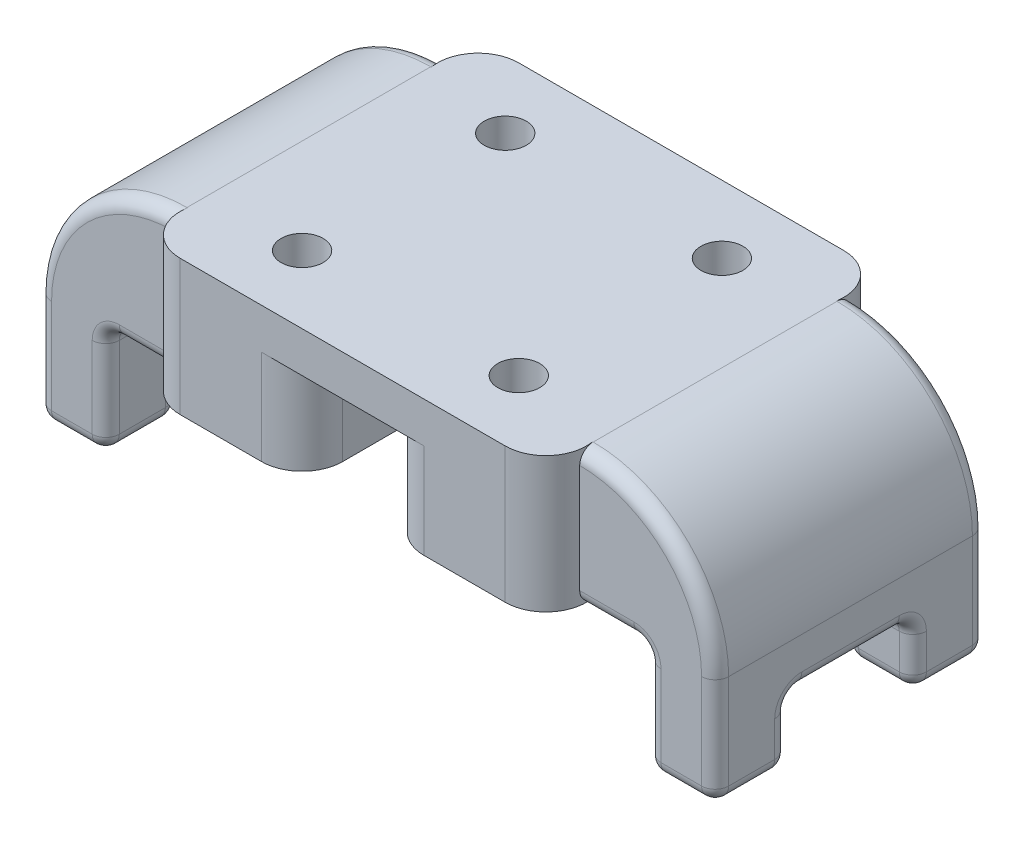
SolidWorks part; units mm, degrees
ref_plane "Front" through (0, 0, 0) normal (0, 0, 1) x (1, 0, 0)
ref_plane "Top" through (0, 0, 0) normal (0, 1, 0) x (1, 0, 0)
ref_plane "Right" through (0, 0, 0) normal (1, 0, 0) x (0, 0, -1)
sketch "草图1" plane through (0, 0, 0) normal (0, 1, 0) x (1, 0, 0)
  line L1 (-15, -12.5) -> (15, -12.5)
  line L2 (-15, -12.5) -> (-15, 12.5)
  line L3 (-15, 12.5) -> (15, 12.5)
  line L4 (15, -12.5) -> (15, 12.5)
  line L5 (-15, -12.5) -> (15, 12.5) construction
  line L6 (-15, 12.5) -> (15, -12.5) construction
  point P0 (0, 0)
  dimension "D1" = 30
  dimension "D2" = 25
extrude "凸台-拉伸1" add sketch "草图1" along normal blind 10
sketch "草图2" plane through (0, 10, 0) normal (0, 1, 0) x (1, 0, 0)
  line L0 (-10.2649, 0) -> (11.3071, 0) construction
  line L1 (0, -5.7957) -> (0, 6.2063) construction
  circle A0 centre (-8, 7.5) radius 1.55
  circle A1 centre (-8, -7.5) radius 1.55
  circle A2 centre (8, -7.5) radius 1.55
  circle A3 centre (8, 7.5) radius 1.55
  dimension "D1" = 3.1
  dimension "D2" = 8
  dimension "D3" = 7.5
extrude "切除-拉伸1" cut sketch "草图2" against normal through all
sketch "草图4" plane through (0, 0, 0) normal (0, -1, 0) x (1, 0, 0)
  line L0 (3, 12.5) -> (3, -12.5)
  line L1 (-15, 12.5) -> (15, 12.5) construction
  line L2 (15, -12.5) -> (-15, -12.5) construction
  line L3 (-3, 9.5) -> (-3, -9.5)
  line L4 (-6, -12.5) -> (-13, -12.5) construction
  line L5 (-6, 12.5) -> (-13, 12.5) construction
  line L6 (-13, -12.5) -> (-13, 12.5) construction
  line L7 (-8, 7.5) -> (-8, -49992.5) construction
  line L8 (8, 7.5) -> (8, -49992.5) construction
  line L9 (-6, 12.5) -> (3, 12.5)
  line L10 (-6, -12.5) -> (3, -12.5)
  arc A0 (-6, -12.5) -> (-3, -9.5) centre (-6, -9.5) ccw
  arc A1 (-3, 9.5) -> (-6, 12.5) centre (-6, 9.5) ccw
  point P12 (-3, -12.5)
  point P15 (-3, 12.5)
  dimension "D2" = 3
  dimension "D1" = 10
  dimension "D3" = 6
  dimension "D4" = 5
extrude "切除-拉伸2" cut sketch "草图4" against normal blind 7
fillet "圆角1" radius 3 4 edges at (15, 5, 12.5) (15, 5, -12.5) (-15, 5, -12.5) (-15, 5, 12.5)
sketch "草图5" plane through (0, 0, 0) normal (0, -1, 0) x (1, 0, 0)
  line L0 (0, 0) -> (0, -50000) construction
  line L1 (0, 0) -> (50000, 0) construction
  line L2 (-15, -9.5) -> (-15, 9.5) construction
  line L3 (-25, -10) -> (-15, -10)
  line L4 (-25, -10) -> (-25, 10)
  line L5 (-25, 10) -> (-15, 10)
  line L6 (-15, -10) -> (-15, 10)
  line L7 (-25, -10) -> (-15, 10) construction
  line L8 (-25, 10) -> (-15, -10) construction
  line L9 (25, 10) -> (15, 10)
  line L10 (15, -10) -> (15, 10)
  line L11 (25, -10) -> (15, -10)
  line L12 (25, -10) -> (25, 10)
  line L13 (25, 10) -> (15, -10) construction
  line L14 (25, -10) -> (15, 10) construction
  point P5 (-20, 0)
  point P16 (20, 0)
  dimension "D1" = 20
  dimension "D2" = 50
extrude "凸台-拉伸2" add sketch "草图5" against normal blind 10
sketch "草图6" plane through (0, 0, 0) normal (0, -1, 0) x (1, 0, 0)
  line L1 (-25, 10) -> (-20, 10)
  line L2 (-25, 10) -> (-25, -10)
  line L3 (-25, -10) -> (-20, -10)
  line L4 (-20, 10) -> (-20, -10)
  line L5 (-25, -10) -> (-15, -10) construction
  line L6 (0, 0) -> (0, -50000) construction
  line L7 (20, 10) -> (20, -10)
  line L8 (25, -10) -> (20, -10)
  line L9 (25, 10) -> (25, -10)
  line L10 (25, 10) -> (20, 10)
  dimension "D1" = 20
  dimension "D2" = 5
extrude "凸台-拉伸3" add sketch "草图6" along normal blind 8
sketch "草图7" plane through (25, 0, 0) normal (1, 0, 0) x (0, 0, -1)
  line L0 (0, 0) -> (0, -50000) construction
  line L1 (10, -8) -> (-10, -8) construction
  line L3 (-4.6, -3.4) -> (4.6, -3.4)
  line L4 (-4.6, -3.4) -> (-4.6, -8)
  line L5 (-4.6, -8) -> (4.6, -8)
  line L6 (4.6, -3.4) -> (4.6, -8)
  line L7 (-4.6, -3.4) -> (4.6, -8) construction
  line L8 (-4.6, -8) -> (4.6, -3.4) construction
  point P3 (0, -5.7)
  dimension "D1" = 4.6
  dimension "D2" = 9.2
extrude "切除-拉伸3" cut sketch "草图7" against normal through all
fillet "圆角6" radius 3 2 edges at (3, 3.5, 12.5) (3, 3.5, -12.5)
fillet "圆角3" radius 10 2 edges at (25, 10, 0) (-25, 10, 0)
fillet "圆角4" radius 1 25 edges at (20, -5.7, -4.6) (20, -5.7, 4.6) (25, -5.7, 4.6) (25, -5.7, -4.6) (22.0711, 7.0711, 10) (22.0711, 7.0711, -10) (20, -8, 7.3) (22.5, -8, 10) (25, -8, 7.3) (22.5, -8, 4.6) (20, -3.4, 0) (22.5, -3.4, 4.6) (25, -3.4, 0) (22.5, -3.4, -4.6) (25, -8, -7.3) (22.5, -8, -10) (20, -8, -7.3) (22.5, -8, -4.6) (25, -4, 10) (25, -4, -10) (17.5, 0, -10) (17.5, 0, 10) (20, -4, -10) (20, 0, 0) (20, -4, 10)
fillet "圆角5" radius 1 25 edges at (-17.5, 0, 10) (-17.5, 0, -10) (-25, -5.7, -4.6) (-25, -5.7, 4.6) (-22.0711, 7.0711, 10) (-22.0711, 7.0711, -10) (-20, -5.7, 4.6) (-20, -4, 10) (-20, 0, 0) (-20, -4, -10) (-20, -5.7, -4.6) (-20, -8, -7.3) (-22.5, -8, -10) (-25, -8, -7.3) (-22.5, -8, -4.6) (-20, -3.4, 0) (-22.5, -3.4, -4.6) (-25, -3.4, 0) (-22.5, -3.4, 4.6) (-25, -8, 7.3) (-22.5, -8, 10) (-20, -8, 7.3) (-22.5, -8, 4.6) (-25, -4, 10) (-25, -4, -10)
equation "\"7。5\"=4"
